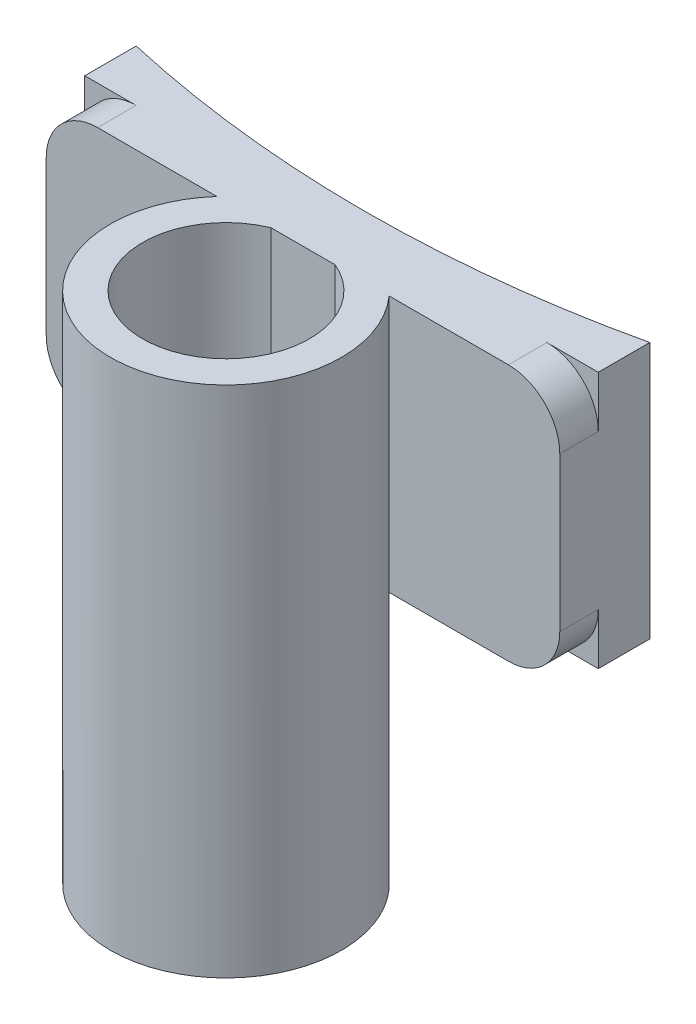
SolidWorks part; units mm, degrees
ref_plane "Front Plane" through (0, 0, 0) normal (0, 0, 1) x (1, 0, 0)
ref_plane "Top Plane" through (0, 0, 0) normal (0, 1, 0) x (1, 0, 0)
ref_plane "Right Plane" through (0, 0, 0) normal (1, 0, 0) x (0, 0, -1)
sketch "Sketch1" plane through (0, 0, 0) normal (0, 1, 0) x (1, 0, 0)
  circle A0 centre (0, 0) radius 3.25
  circle A1 centre (0, 0) radius 4.5
  dimension "D1" = 6.5
  dimension "D2" = 9
extrude "Boss-Extrude1" add sketch "Sketch1" along normal blind 20
ref_plane "Plane1" through (0, 0, -4.5) normal (0, 0, 1) x (1, 0, 0)
sketch "Sketch2" plane through (0, 0, -4.5) normal (0, 0, 1) x (1, 0, 0)
  line L0 (-4.5, 10) -> (4.5, 10) construction
  line L1 (-4.5, 20) -> (-4.5, 0) construction
  line L2 (4.5, 0) -> (4.5, 20) construction
  line L3 (0, 10) -> (0, 15) construction
  line L4 (-10, 20) -> (-4.5, 10) construction
  line L5 (-10, 20) -> (10, 20)
  line L6 (-10, 20) -> (-10, 10)
  line L7 (-10, 10) -> (10, 10)
  line L8 (10, 20) -> (10, 10)
  line L9 (-10, 20) -> (10, 10) construction
  line L10 (-10, 10) -> (10, 20) construction
  line L11 (4.5, 10) -> (10, 20) construction
  circle A0 centre (-7.25, 15) radius 2
  circle A1 centre (7.25, 15) radius 2
  dimension "D4" = 4
  dimension "D1" = 5
  dimension "D2" = 10
  dimension "D3" = 20
extrude "Boss-Extrude2" add sketch "Sketch2" along normal mid plane 3 contours L6 L5 L8 L7
fillet "Fillet1" radius 2 4 edges at (-10, 10, -4.5) (-10, 20, -4.5) (10, 10, -4.5) (10, 20, -4.5)
sketch "Sketch3" plane through (0, 0, -6) normal (0, 0, -1) x (-1, 0, 0)
  circle A2 centre (-7.25, 15) radius 2 construction
  circle A3 centre (-7.25, 15) radius 2
extrude "Boss-Extrude3" add sketch "Sketch2<4>" against normal blind 3
sketch "Sketch2<4>" plane through (0, 0, -4.5) normal (0, 0, 1) x (1, 0, 0) same geometry as "Sketch2"
sketch "Sketch4" plane through (0, 20, 0) normal (0, 1, 0) x (1, 0, 0)
  circle A0 centre (0, 50.3797) radius 45
  point P2 (0, 50.3797)
  dimension "D1" = 90
extrude "Cut-Extrude1" cut sketch "Sketch4" against normal blind 10
